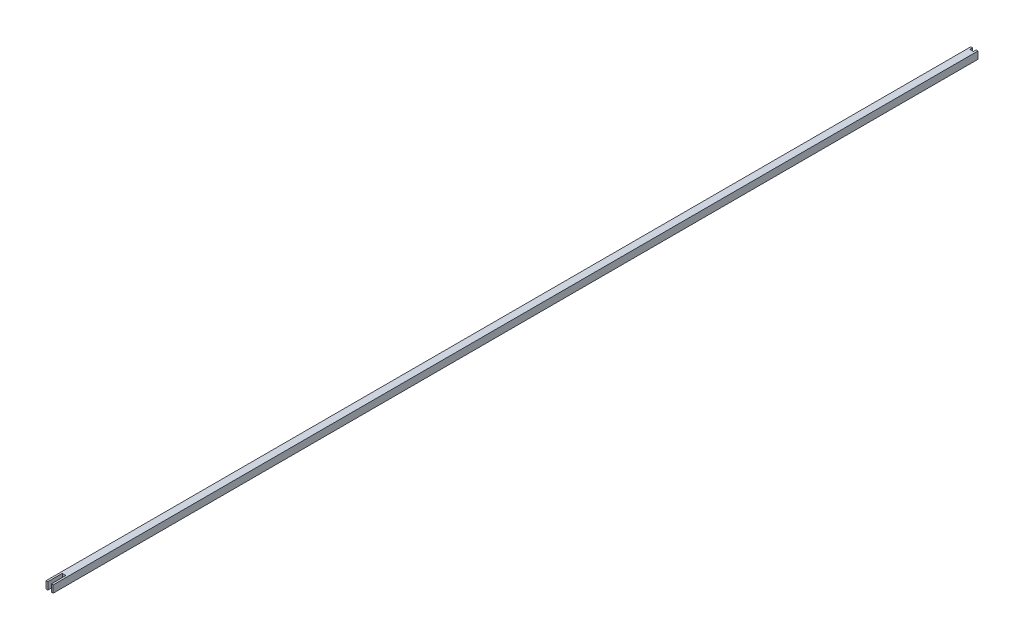
SolidWorks part; units mm, degrees
ref_plane "Front Plane" through (0, 0, 0) normal (1, 0, 0) x (0, 1, 0)
ref_plane "Top Plane" through (0, 0, 0) normal (0, 0, 1) x (0, 1, 0)
ref_plane "Right Plane" through (0, 0, 0) normal (0, 1, 0) x (-1, 0, 0)
sketch "Sketch1" plane through (0, 0, 0) normal (0, 1, 0) x (-1, 0, 0)
  line L0 (0, 0) -> (1.5875, 0)
  line L1 (1.5875, 0) -> (1.5875, 2.3812)
  line L2 (1.5875, 2.3812) -> (4.7625, 2.3812)
  line L3 (4.7625, 2.3812) -> (4.7625, 0)
  line L4 (4.7625, 0) -> (6.35, 0)
  line L5 (6.35, 0) -> (6.35, 812.8)
  line L6 (6.35, 812.8) -> (4.7625, 812.8)
  line L7 (4.7625, 812.8) -> (4.7625, 800.1)
  line L8 (4.7625, 800.1) -> (1.5875, 800.1)
  line L9 (1.5875, 800.1) -> (1.5875, 812.8)
  line L10 (1.5875, 812.8) -> (0, 812.8)
  line L11 (0, 812.8) -> (0, 0)
extrude "Boss-Extrude1" add sketch "Sketch1" along normal blind 6.35
